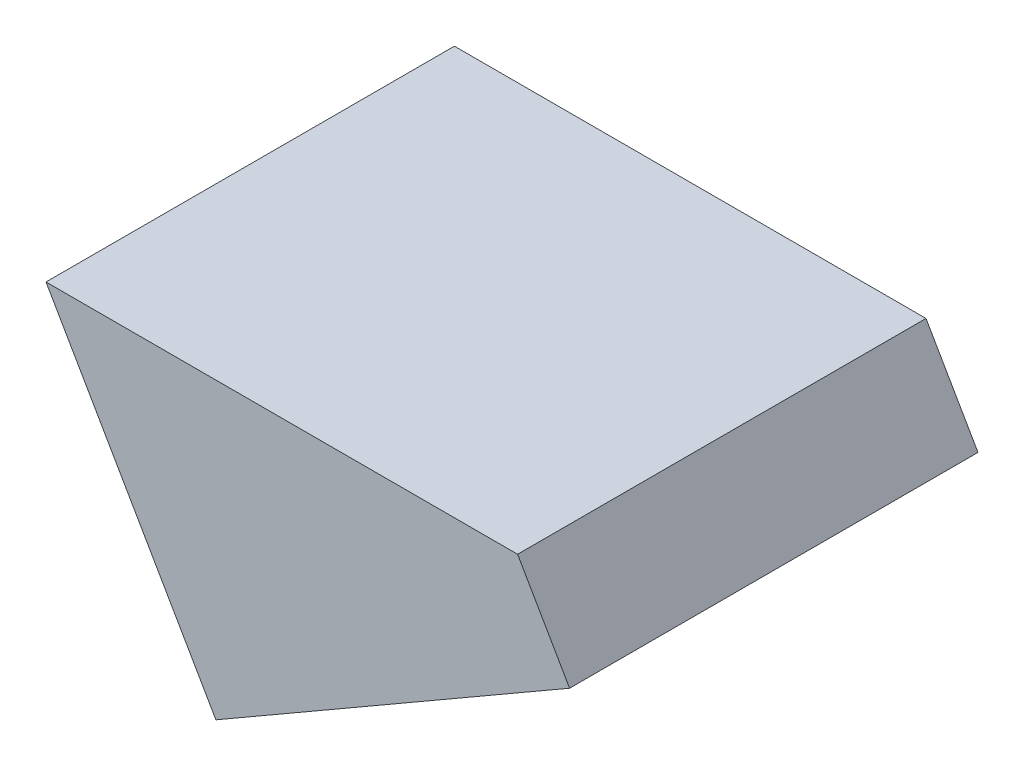
SolidWorks part; units mm, degrees
ref_plane "Plano frontal" through (0, 0, 0) normal (0, 0, 1) x (1, 0, 0)
ref_plane "Plano superior" through (0, 0, 0) normal (0, 1, 0) x (1, 0, 0)
ref_plane "Plano direito" through (0, 0, 0) normal (1, 0, 0) x (0, 0, -1)
sketch "Esboço1" plane through (0, 0, 0) normal (0, 1, 0) x (1, 0, 0)
  line L5 (-15, -15) -> (15, -15)
  line L6 (-15, -15) -> (-15, 15)
  line L7 (-15, 15) -> (15, 15)
  line L8 (15, -15) -> (15, 15)
  line L9 (-15, -15) -> (15, 15) construction
  line L10 (-15, 15) -> (15, -15) construction
  point P0 (0, 0)
  dimension "D1" = 30
  dimension "D2" = 30
extrude "Ressalto-extrusão1" add sketch "Esboço1" along normal blind 22.775
sketch "Esboço2" plane through (0, 0, 15) normal (0, 0, 1) x (1, 0, 0)
  line L7 (-15, 0) -> (15, 17.3205)
  line L8 (15, 22.775) -> (15, 0) construction
  line L9 (15, 17.3205) -> (15, 0)
  line L10 (15, 0) -> (-15, 0)
  line L11 (-15, 22.775) -> (15, 22.775) construction
  point P5 (15, 12.7156)
  dimension "D1" = 30
extrude "Corte-extrusão1" cut sketch "Esboço2" against normal through all
sketch "Esboço3" plane through (-3.75, 6.4952, 0) normal (0.5, -0.866, 0) x (0.866, 0.5, 0)
  line L5 (21.6506, 15) -> (-12.9904, 15) construction
  line L7 (-10.6699, 15) -> (19.3301, 15)
  line L8 (-10.6699, 15) -> (-10.6699, -15)
  line L9 (-10.6699, -15) -> (19.3301, -15)
  line L10 (19.3301, 15) -> (19.3301, -15)
  line L11 (-10.6699, 15) -> (19.3301, -15) construction
  line L12 (-10.6699, -15) -> (19.3301, 15) construction
  line L13 (21.6506, -15) -> (21.6506, 15) construction
  point P0 (4.3301, 0)
  point P7 (21.6506, 0)
  point P8 (10.8648, -3.0956)
  point P9 (6.7597, -1.5478)
  point P12 (4.3301, 15)
  point P15 (19.3301, 0)
  dimension "D1" = 30
  dimension "D2" = 30
extrude "Corte-extrusão2" cut sketch "Esboço3" against normal through all flip side to cut
sketch "Esboço4" plane through (0, 0, 15) normal (0, 0, 1) x (1, 0, 0)
  line L0 (-25.4697, 22.775) -> (-15, 4.641)
  line L1 (-25.4697, 22.775) -> (-15, 22.775)
  line L2 (-15, 22.775) -> (9.1714, 22.775) construction
  line L3 (-15, 4.641) -> (-12.9904, 1.1603) construction
  line L4 (-15, 22.775) -> (-15, 4.641) construction
  line L5 (-15, 22.775) -> (-15, 4.641)
extrude "Ressalto-extrusão2" add sketch "Esboço4" against normal blind 30
